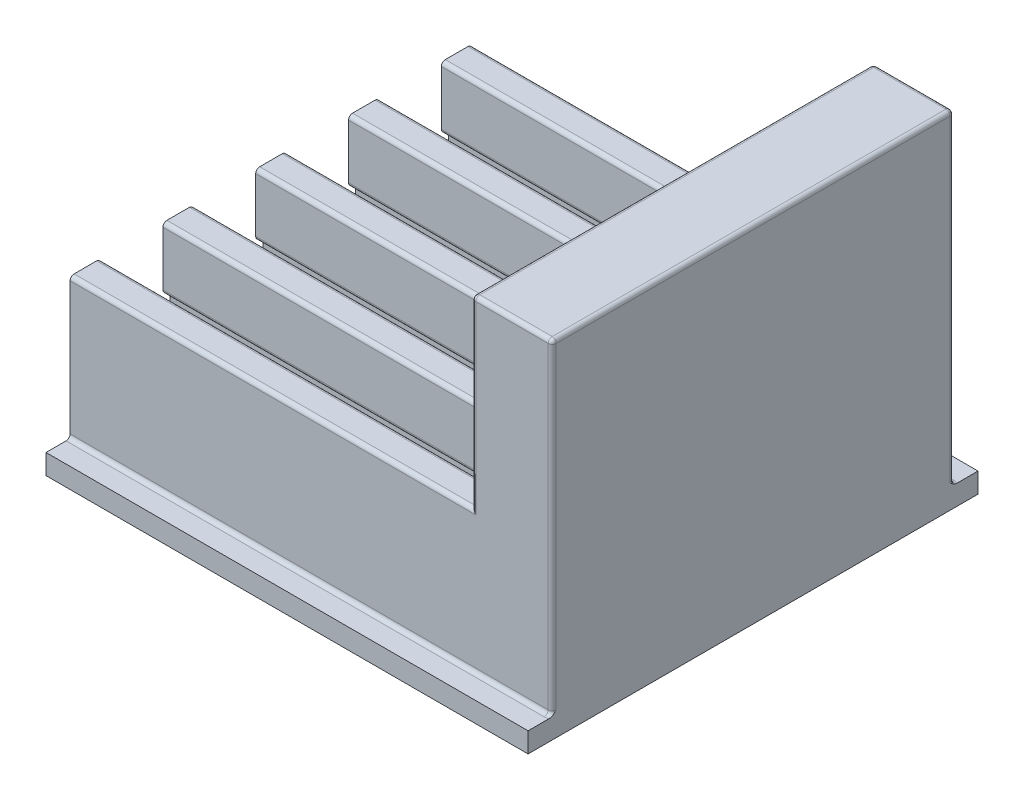
SolidWorks part; units mm, degrees
ref_plane "Front Plane" through (0, 0, 0) normal (0, 0, 1) x (1, 0, 0)
ref_plane "Top Plane" through (0, 0, 0) normal (0, 1, 0) x (1, 0, 0)
ref_plane "Right Plane" through (0, 0, 0) normal (1, 0, 0) x (0, 0, -1)
sketch "Sketch1" plane through (0, 0, 0) normal (0, 1, 0) x (1, 0, 0)
  line L1 (-63.5354, 42.4181) -> (56.4646, 42.4181)
  line L2 (-63.5354, 42.4181) -> (-63.5354, -57.5819)
  line L3 (-63.5354, -57.5819) -> (56.4646, -57.5819)
  line L4 (56.4646, 42.4181) -> (56.4646, -57.5819)
  dimension "D1" = 100
  dimension "D2" = 120
extrude "Boss-Extrude1" add sketch "Sketch1" along normal blind 81
sketch "Sketch2" plane through (0, 81, 0) normal (0, 1, 0) x (1, 0, 0)
  line L0 (-63.5354, -57.5819) -> (56.4646, -57.5819) construction
  line L1 (-63.5354, 42.4181) -> (36.4646, 42.4181)
  line L2 (-63.5354, 42.4181) -> (-63.5354, -57.5819)
  line L3 (-63.5354, -57.5819) -> (36.4646, -57.5819)
  line L4 (36.4646, 42.4181) -> (36.4646, -57.5819)
  dimension "D1" = 100
extrude "Cut-Extrude1" cut sketch "Sketch2" against normal blind 46
sketch "Sketch6" plane through (-63.5354, 0, 0) normal (-1, 0, 0) x (0, 0, 1)
  line L0 (57.5819, 35) -> (-42.4181, 35) construction
  line L1 (-34.8181, 35) -> (-19.3181, 35)
  line L2 (-34.8181, 35) -> (-34.8181, 19.5)
  line L3 (-34.8181, 19.5) -> (-19.3181, 19.5)
  line L4 (-19.3181, 35) -> (-19.3181, 19.5)
  line L5 (-19.3181, 27.25) -> (-11.7181, 27.25) construction
  line L6 (-11.7181, 35) -> (3.7819, 35)
  line L7 (-11.7181, 35) -> (-11.7181, 19.5)
  line L8 (-11.7181, 19.5) -> (3.7819, 19.5)
  line L9 (3.7819, 35) -> (3.7819, 19.5)
  line L10 (11.3819, 35) -> (26.8819, 35)
  line L11 (11.3819, 35) -> (11.3819, 19.5)
  line L12 (11.3819, 19.5) -> (26.8819, 19.5)
  line L13 (26.8819, 35) -> (26.8819, 19.5)
  line L14 (34.4819, 35) -> (49.9819, 35)
  line L15 (34.4819, 35) -> (34.4819, 19.5)
  line L16 (34.4819, 19.5) -> (49.9819, 19.5)
  line L17 (49.9819, 35) -> (49.9819, 19.5)
  line L18 (-15.5181, 27.25) -> (-15.5181, 0) construction
  line L19 (-42.4181, 0) -> (57.5819, 0) construction
  line L20 (7.5819, 35) -> (7.5819, 0) construction
  line L21 (-42.4181, 35) -> (57.5819, 35) construction
  circle A0 centre (-27.0681, 27.25) radius 5.95
  circle A1 centre (-3.9681, 27.25) radius 5.95
  circle A2 centre (42.2319, 27.25) radius 5.95
  circle A3 centre (19.1319, 27.25) radius 5.95
  dimension "D13" = 7.75
  dimension "D1" = 15.5
  dimension "D2" = 15.5
  dimension "D3" = 15.5
  dimension "D4" = 15.5
  dimension "D5" = 15.5
  dimension "D6" = 15.5
  dimension "D7" = 15.5
  dimension "D8" = 15.5
  dimension "D9" = 7.6
  dimension "D10" = 7.6
  dimension "D11" = 7.6
  dimension "D12" = 7.6
  dimension "D14" = 7.75
extrude "Cut-Extrude4" cut sketch "Sketch6" against normal blind 100 contours L11 L10 L13 L12 | L15 L14 L17 L16 | L7 L6 L9 L8 | L2 L1 L4 L3
sketch "Sketch8" plane through (-63.5354, 0, 0) normal (-1, 0, 0) x (0, 0, 1)
  line L1 (-36.6181, 19.5) -> (-17.5181, 19.5)
  line L2 (-36.6181, 19.5) -> (-36.6181, 9.5)
  line L3 (-36.6181, 9.5) -> (-17.5181, 9.5)
  line L4 (-17.5181, 19.5) -> (-17.5181, 9.5)
  line L6 (-15.5181, 35) -> (-15.5181, 0) construction
  line L7 (-19.3181, 35) -> (-11.7181, 35) construction
  line L8 (-42.4181, 0) -> (57.5819, 0) construction
  line L9 (5.5819, 9.5) -> (-13.5181, 9.5)
  line L10 (-13.5181, 19.5) -> (-13.5181, 9.5)
  line L11 (5.5819, 19.5) -> (-13.5181, 19.5)
  line L12 (5.5819, 19.5) -> (5.5819, 9.5)
  line L13 (7.5819, 35) -> (7.5819, 0) construction
  line L14 (11.3819, 35) -> (3.7819, 35) construction
  line L15 (51.7819, 9.5) -> (32.6819, 9.5)
  line L16 (32.6819, 19.5) -> (32.6819, 9.5)
  line L17 (51.7819, 19.5) -> (32.6819, 19.5)
  line L18 (51.7819, 19.5) -> (51.7819, 9.5)
  line L19 (9.5819, 19.5) -> (9.5819, 9.5)
  line L20 (9.5819, 19.5) -> (28.6819, 19.5)
  line L21 (28.6819, 19.5) -> (28.6819, 9.5)
  line L22 (9.5819, 9.5) -> (28.6819, 9.5)
  dimension "D1" = 1.8
  dimension "D2" = 10
  dimension "D3" = 19.1
extrude "Cut-Extrude5" cut sketch "Sketch8" against normal blind 100
extrude "Cut-Extrude6" cut sketch "Sketch6<3>" against normal blind 111 contours A0 | A1 | A3 | A2 region at (-63.5354, 27.25, -27.0681) region at (-63.5354, 27.25, -3.9681) region at (-63.5354, 27.25, 42.2319) region at (-63.5354, 27.25, 19.1319)
sketch "Sketch6<3>" plane through (-63.5354, 0, 0) normal (-1, 0, 0) x (0, 0, 1) same geometry as "Sketch6"
fillet "Fillet1" radius 1 10 edges at (-13.5354, 35, -42.4181) (-13.5354, 35, 57.5819) (36.4646, 58, -42.4181) (36.4646, 58, 57.5819) (46.4646, 81, 57.5819) (36.4646, 81, 7.5819) (46.4646, 81, -42.4181) (56.4646, 81, 7.5819) (56.4646, 40.5, 57.5819) (56.4646, 40.5, -42.4181)
chamfer "Chamfer1" distance 1 angle 45 4 edges at (36.4646, 27.25, 36.2819) (36.4646, 27.25, 13.1819) (36.4646, 27.25, -9.9181) (36.4646, 27.25, -33.0181)
fillet "Fillet2" radius 1 4 edges at (47.4646, 27.25, 48.1819) (47.4646, 27.25, 25.0819) (47.4646, 27.25, 1.9819) (47.4646, 27.25, -21.1181)
fillet "Fillet3" radius 1 16 edges at (-13.5354, 19.5, -19.3181) (-13.5354, 19.5, 3.7819) (-13.5354, 19.5, 26.8819) (-13.5354, 19.5, -34.8181) (-13.5354, 19.5, -11.7181) (-13.5354, 19.5, 11.3819) (-13.5354, 19.5, 34.4819) (-13.5354, 19.5, 49.9819) (-13.5354, 35, -34.8181) (-13.5354, 35, -19.3181) (-13.5354, 35, -11.7181) (-13.5354, 35, 3.7819) (-13.5354, 35, 26.8819) (-13.5354, 35, 11.3819) (-13.5354, 35, 34.4819) (-13.5354, 35, 49.9819)
sketch "Sketch9" plane through (0, 0, 0) normal (0, -1, 0) x (1, 0, 0)
  line L0 (56.4646, 56.5819) -> (56.4646, -41.4181) construction
  line L1 (-63.5354, 63.5819) -> (56.4646, 63.5819)
  line L2 (-63.5354, 63.5819) -> (-63.5354, -48.4181)
  line L3 (-63.5354, -48.4181) -> (56.4646, -48.4181)
  line L4 (56.4646, 63.5819) -> (56.4646, -48.4181)
  line L5 (-63.5354, -42.4181) -> (-63.5354, 57.5819) construction
  line L6 (-63.5354, 57.5819) -> (55.4646, 57.5819) construction
  line L7 (55.4646, -42.4181) -> (-63.5354, -42.4181) construction
  dimension "D1" = 6
  dimension "D2" = 6
extrude "Boss-Extrude2" add sketch "Sketch9" along normal blind 5
fillet "Fillet4" radius 1 4 edges at (56.1717, 0, 57.289) (56.1717, 0, -42.1252) (-4.0354, 0, 57.5819) (-4.0354, 0, -42.4181)
